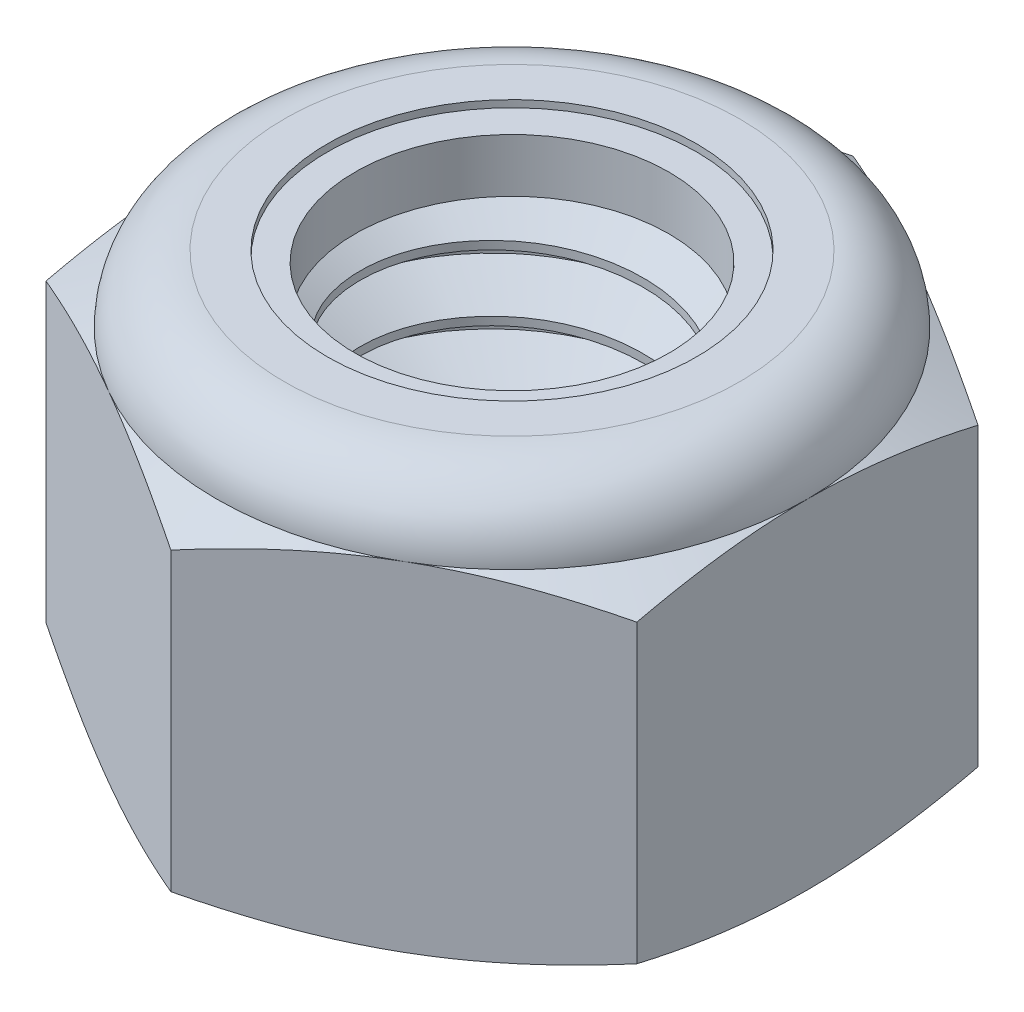
SolidWorks part; units mm, degrees
material "Plain Carbon Steel"
ref_plane "Front" through (0, 0, 0) normal (0, 0, 1) x (1, 0, 0)
ref_plane "Top" through (0, 0, 0) normal (0, 1, 0) x (1, 0, 0)
ref_plane "Right" through (0, 0, 0) normal (1, 0, 0) x (0, 0, -1)
sketch "Sketch8" plane through (0, 0, 0) normal (1, 0, 0) x (0, 0, -1)
  line L0 (0, 0) -> (0, 8.7312) construction
  line L1 (6.35, 0) -> (-6.35, 0) construction
  line L2 (-3.9688, 8.7312) -> (3.9688, 8.7312) construction
  line L3 (3.9688, 8.7312) -> (3.9687, 7.3201) construction
  point P7 (-3.3734, 8.7312)
  dimension "D1" = 6.7469
sketch "Sketch1" plane through (0, 0, 0) normal (0, 1, 0) x (1, 0, 0)
  line L1 (0, 7.3323) -> (-6.35, 3.6662)
  line L2 (-6.35, 3.6662) -> (-6.35, -3.6662)
  line L3 (-6.35, -3.6662) -> (0, -7.3323)
  line L4 (0, -7.3323) -> (6.35, -3.6662)
  line L5 (6.35, -3.6662) -> (6.35, 3.6662)
  line L6 (6.35, 3.6662) -> (0, 7.3323)
  circle A0 centre (0, 0) radius 6.35 construction
  circle A1 centre (0, 0) radius 3.9688
extrude "Extrude1" add sketch "Sketch1" along normal up to vertex (8.7312 mm away) up to point (0, 8.7312, 0)
sketch "Sketch5" plane through (0, 0, 0) normal (1, 0, 0) x (0, 0, -1)
  line L0 (0, 0) -> (6.35, 0)
  line L1 (6.35, 0) -> (7.3323, 0.4581)
  line L2 (7.3323, 0.4581) -> (7.3323, 6.818)
  line L3 (7.3323, 6.818) -> (6.35, 7.276)
  line L4 (4.8948, 8.7312) -> (4.8948, 10.0012)
  line L5 (4.8948, 10.0012) -> (8.6023, 10.0012)
  line L6 (8.6023, 10.0012) -> (8.6023, -1.27)
  line L7 (8.6023, -1.27) -> (0, -1.27)
  line L8 (0, -1.27) -> (0, 0)
  line L9 (6.35, 7.276) -> (6.35, 0) construction
  line L12 (7.3323, 8.7312) -> (7.3323, 0) construction
  line L13 (7.3323, 4.3656) -> (8.6023, 4.3656) construction
  line L15 (0, 0) -> (0, 10.0012) construction
  line L18 (6.35, 0) -> (-6.35, 0) construction
  line L19 (3.6662, 8.7312) -> (7.3323, 8.7312) construction
  line L20 (0, 10.0012) -> (4.8948, 10.0012) construction
  line L21 (3.6662, 0) -> (7.3323, 0) construction
  arc A0 (6.35, 7.276) -> (4.8948, 8.7312) centre (4.8948, 7.276) ccw
  dimension "D1" = 25
  dimension "D2" = 1.27
  dimension "D4" = 1.4552
revolve "Cut-Revolve3" cut sketch "Sketch5" angle 360 about L15
sketch "Sketch4" plane through (0, 0, 0) normal (1, 0, 0) x (0, 0, -1)
  line L0 (0, 7.276) -> (4.3656, 7.276)
  line L1 (4.3656, 7.276) -> (0, 5.2403)
  line L3 (0, 2.0357) -> (4.3656, 0)
  line L4 (4.3656, 0) -> (0, 0)
  line L5 (0, 0) -> (0, 7.276) construction
  line L10 (0, 0) -> (0, 8.7312) construction
  line L11 (0, 2.0357) -> (0, 0)
  line L12 (0, 7.276) -> (0, 5.2403)
  line L13 (5.4993, 7.276) -> (0, 7.276) construction
  dimension "D1" = 25
  dimension "D2" = 8.7312
sketch "Sketch6" plane through (0, 0, 0) normal (1, 0, 0) x (0, 0, -1)
  line L0 (0, 7.276) -> (6.1976, 7.276)
  line L1 (4.8948, 8.5788) -> (2.4474, 8.5788)
  line L2 (0, 10.0012) -> (0, 7.276)
  line L3 (2.4474, 10.0012) -> (0, 10.0012)
  line L4 (0, 10.0012) -> (4.8948, 10.0012) construction
  line L5 (0, 0) -> (0, 10.0012) construction
  line L6 (0, 10.0012) -> (0, 0) construction
  line L7 (2.4474, 8.5788) -> (2.4474, 10.0012)
  line L8 (4.8948, 8.7312) -> (4.8948, 8.5788) construction
  line L9 (2.4474, 8.5788) -> (0, 8.5788) construction
  line L10 (0, 8.5788) -> (0, 5.2403) construction
  arc A0 (6.1976, 7.276) -> (4.8948, 8.5788) centre (4.8948, 7.276) ccw
  arc A1 (6.35, 7.276) -> (4.8948, 8.7312) centre (4.8948, 7.276) ccw construction
  dimension "D1" = 0.1524
revolve "Cut-Revolve4" cut sketch "Sketch6" angle 360 about L6
revolve "Cut-Revolve2" cut sketch "Sketch4" angle 360 about L5
sketch "Sketch7" plane through (0, 0, 0) normal (1, 0, 0) x (0, 0, -1)
  line L0 (3.3734, 7.3522) -> (6.119, 7.3522)
  line L1 (4.8948, 8.5027) -> (3.3734, 8.5027)
  line L2 (3.3734, 8.5027) -> (3.3734, 7.3522)
  line L3 (3.3734, 7.3522) -> (0, 7.3522) construction
  line L4 (0, 7.3522) -> (0, 8.5027) construction
  line L5 (0, 8.5027) -> (3.3734, 8.5027) construction
  line L6 (3.3734, 7.3522) -> (3.3734, 7.276) construction
  line L7 (0, 7.276) -> (6.1976, 7.276) construction
  line L8 (4.8948, 8.5027) -> (4.8948, 8.5788) construction
  arc A0 (6.119, 7.3522) -> (4.8948, 8.5027) centre (4.8948, 7.276) ccw
  arc A2 (6.1976, 7.276) -> (4.8948, 8.5788) centre (4.8948, 7.276) ccw construction
  dimension "D1" = 0.0762
  dimension "D2" = 6.7469
revolve "Revolve2" add sketch "Sketch7" angle 360 about L4
sketch "Sketch2" plane through (0, 0, 0) normal (1, 0, 0) x (0, 0, -1)
  line L0 (-3.9688, 0) -> (-3.9688, 7.276) construction
  line L1 (0, 0) -> (3.9688, 0)
  line L2 (0, 0) -> (0, 7.276)
  line L3 (0, 7.276) -> (3.9688, 7.276)
  line L4 (3.9688, 0) -> (3.9688, 7.276)
  line L6 (5.4993, 7.276) -> (6.35, 7.276) construction
  line L7 (0, -3.9688) -> (0, 0) construction
revolve "Revolve1" add sketch "Sketch2" angle 360 about L7
sketch "Sketch9" plane through (0, 0, 0) normal (1, 0, 0) x (0, 0, -1)
  line L0 (4.1215, 8.599) -> (4.1215, 7.1878) construction
  line L1 (4.1215, 7.1878) -> (2.8994, 7.8934) construction
  line L2 (2.8994, 7.8934) -> (4.1215, 8.599) construction
  line L3 (3.0522, 7.9816) -> (3.0522, 7.8052) construction
  line L4 (3.9688, 8.5108) -> (3.9688, 7.276) construction
  line L5 (2.8994, 7.8934) -> (3.0522, 7.8934) construction
  line L6 (3.9688, 7.8934) -> (4.1215, 7.8934) construction
  line L7 (4.0451, 7.8934) -> (4.0451, 8.5549) construction
  line L8 (4.1215, 7.1878) -> (4.0451, 8.5549)
  line L9 (4.0451, 8.5549) -> (3.0522, 7.9816)
  line L10 (3.0522, 7.9816) -> (3.0522, 7.8052)
  line L11 (3.0522, 7.8052) -> (4.1215, 7.1878)
  dimension "D1" = 1.4111
  dimension "D2" = 0.1764
sketch "Sketch10" plane through (0, 7.276, 0) normal (0, 1, 0) x (1, 0, 0)
  circle A1 centre (0, 0) radius 3.9688
  circle A2 centre (0, 0) radius 3.9688
  dimension "D1" = 0
curve "Helix/Spiral1" pitch 1.4111 height 10.1424 turns 7.1875
sweep "Cut-Sweep1" cut profiles "Sketch9" path "Helix/Spiral1" align with end faces yes
sketch "Sketch11" plane through (0, 0, 0) normal (1, 0, 0) x (0, 0, -1)
  line L0 (0, 0) -> (0, 8.7312) construction
  line L1 (6.35, 0) -> (-6.35, 0) construction
  line L4 (0, 8.7312) -> (0, 0) construction
  line L5 (0, 4.3656) -> (3.9688, 4.3656) construction
  line L6 (0, 0) -> (4.3656, 0)
  line L7 (0, 2.0357) -> (0, 0)
  line L8 (4.3656, 0) -> (0, 2.0357)
  dimension "D1" = 8.7312
  dimension "D2" = 25
revolve "Revolve3" add sketch "Sketch11" angle 360 about L4
sketch "Sketch12" plane through (0, 0, 0) normal (1, 0, 0) x (0, 0, -1)
  line L0 (4.3656, 7.276) -> (0, 7.276)
  line L1 (0, 7.276) -> (0, 0)
  line L2 (0, 0) -> (4.3656, 0)
  line L3 (6.35, 0) -> (-6.35, 0) construction
  line L4 (4.3656, 0) -> (4.3656, 7.276)
  line L5 (-4.3656, 0) -> (4.3656, 0) construction
revolve "Revolve4" add sketch "Sketch12" angle 360 about L0
combine bodies "Combine1" operation type subtract main body 136 bodies to subtract 133
equation "\"D4@Sketch5\"=\"Height@Sketch8\"/6"
equation "\"D1@Sketch9\"=\"Thread Pitch@Sketch8\""
equation "\"D2@Sketch9\"=\"Thread Pitch@Sketch8\"/8"
equation "\"D4@Helix/Spiral1\"=\"Thread Pitch@Sketch8\""
equation "\"D3@Helix/Spiral1\"=\"Thread Pitch@Sketch8\"+\"Height@Sketch8\""
equation "\"D2@Sketch4\"=\"Thread Dia@Sketch8\"*1.1"
equation "\"D1@Sketch11\"=\"Thread Dia@Sketch8\"*1.1"
equation "\"D2@Sketch7\"=\"Thread Dia@Sketch8\"*.85"
equation "\"D1@Sketch8\"=\"Thread Dia@Sketch8\"*.85"
